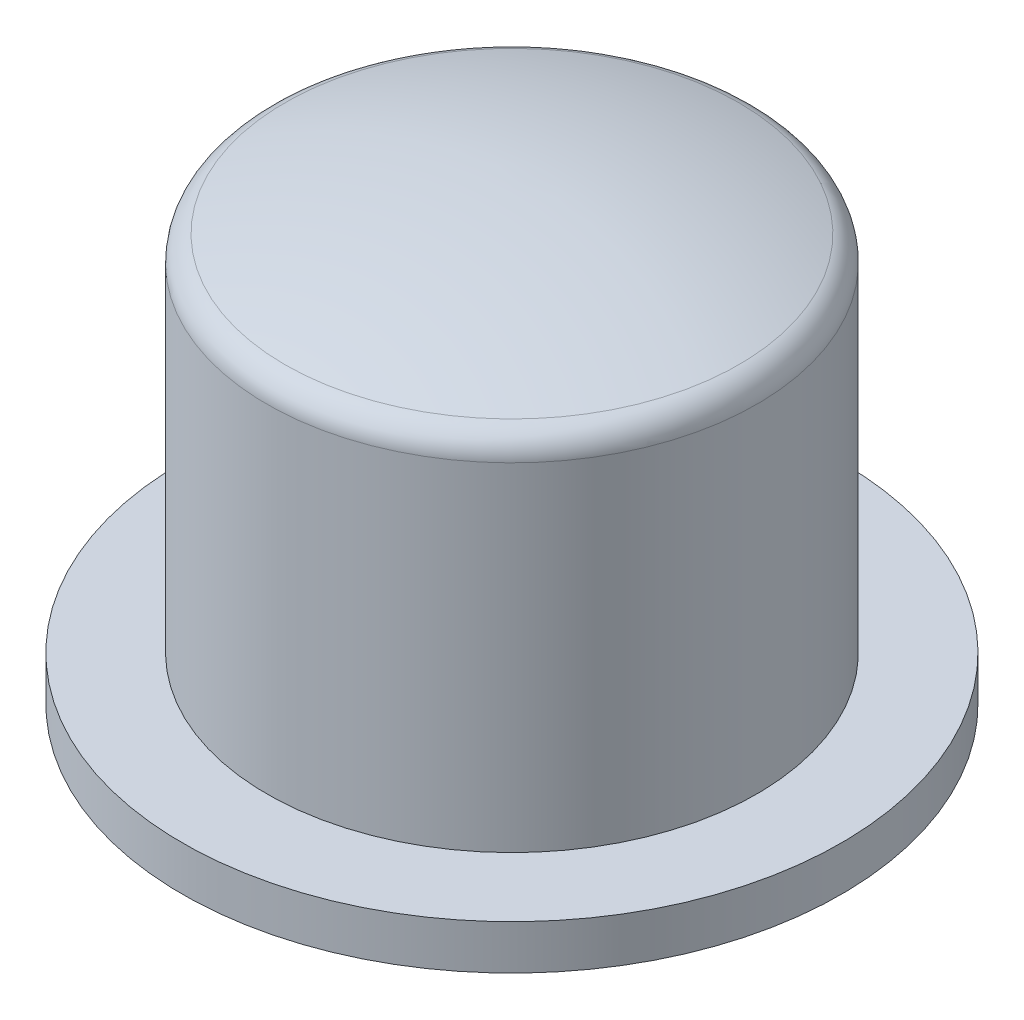
SolidWorks part; units mm, degrees
ref_plane "前视基准面" through (0, 0, 0) normal (0, 0, 1) x (1, 0, 0)
ref_plane "上视基准面" through (0, 0, 0) normal (0, 1, 0) x (1, 0, 0)
ref_plane "右视基准面" through (0, 0, 0) normal (1, 0, 0) x (0, 0, -1)
sketch "草图1" plane through (0, 0, 0) normal (0, 0, 1) x (1, 0, 0)
  line L0 (-3.7, 0) -> (-1.6, 0)
  line L1 (-1.6, 0) -> (-1.6, 3.5)
  line L2 (-2.75, 4.5) -> (0, 4.5)
  line L3 (0, 4.5) -> (0, 3.5)
  line L4 (0, 3.5) -> (-1.6, 3.5)
  line L9 (-2.75, 4.5) -> (-2.75, 0.5)
  line L10 (-2.75, 0.5) -> (-3.7, 0.5)
  line L11 (-3.7, 0.5) -> (-3.7, 0)
  line L13 (0, -1.2166) -> (0, 5.8189) construction
  dimension "D1" = 4.5
  dimension "D2" = 2.75
  dimension "D3" = 1
  dimension "D4" = 1.6
  dimension "D5" = 0.5
revolve "旋转2" add sketch "草图1" angle 360 about L13
dome "圆顶2" faces to dome 1 distance 0.5 reverse direction no elliptical dome no face at (0, 4.5, -2.75) parameters "D1"=0.5
fillet "圆角1" radius 0.3 1 edges at (0, 4.5, -2.75)
